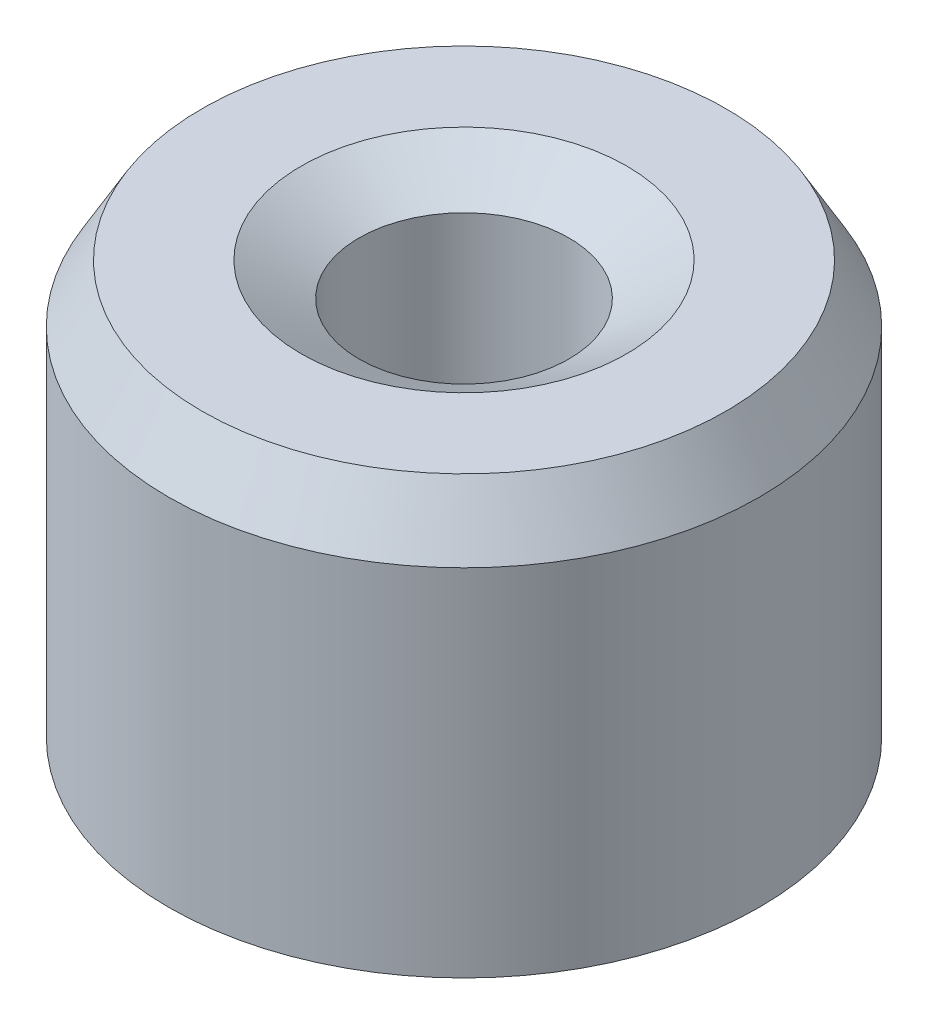
SolidWorks part; units mm, degrees
ref_plane "Front Plane" through (0, 0, 0) normal (0, 0, 1) x (1, 0, 0)
ref_plane "Top Plane" through (0, 0, 0) normal (0, 1, 0) x (1, 0, 0)
ref_plane "Right Plane" through (0, 0, 0) normal (1, 0, 0) x (0, 0, -1)
sketch "Sketch1" plane through (0, 0, 0) normal (0, 1, 0) x (1, 0, 0)
  circle A0 centre (0, 0) radius 15
  dimension "SLEEVE_OD" = 30
extrude "Boss-Extrude1" add sketch "Sketch1" along normal blind 22.6669
sketch "Sketch2" plane through (0, 0, 0) normal (0, 1, 0) x (1, 0, 0)
  circle A0 centre (0, 0) radius 5.3298
  dimension "BORE_D" = 10.6597
extrude "Cut-Extrude1" cut sketch "Sketch2" along normal through all
chamfer "Chamfer1" distance 2.9339 angle 30 4 edges at (0, 22.6669, 5.3298) (0, 0, 5.3298) (0, 0, 15) (0, 22.6669, 15) first distance on face at (0, 22.6669, 5.3298) first distance on face at (0, 0, 5.3298) first distance on face at (0, 22.6669, 15)
